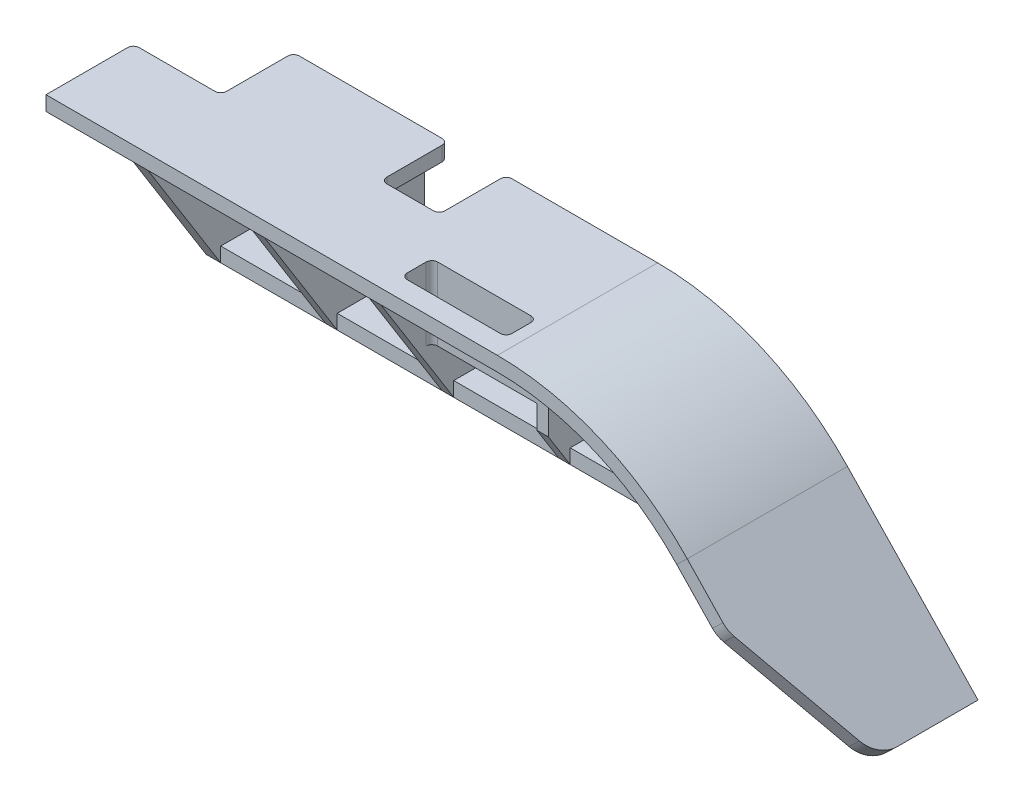
SolidWorks part; units mm, degrees
ref_plane "Front" through (0, 0, 0) normal (0, 0, 1) x (1, 0, 0)
ref_plane "Top" through (0, 0, 0) normal (0, 1, 0) x (1, 0, 0)
ref_plane "Right" through (0, 0, 0) normal (1, 0, 0) x (0, 0, -1)
sketch "Sketch1" plane through (0, 0, 0) normal (0, 1, 0) x (1, 0, 0)
  line L1 (-77.5, 27.5) -> (77.5, 27.5)
  line L2 (-77.5, 27.5) -> (-77.5, -27.5)
  line L3 (-77.5, -27.5) -> (77.5, -27.5)
  line L4 (77.5, 27.5) -> (77.5, -27.5)
  line L5 (-77.5, 27.5) -> (77.5, -27.5) construction
  line L6 (-77.5, -27.5) -> (77.5, 27.5) construction
  point P0 (0, 0)
  dimension "D1" = 155
  dimension "D2" = 55
extrude "Boss-Extrude1" add sketch "Sketch1" along normal blind 5
ref_plane "Plane1" through (0, -40, 0) normal (0, 1, 0) x (1, 0, 0)
sketch "Sketch2" plane through (0, 5, 0) normal (0, 1, 0) x (1, 0, 0)
  line L1 (-77.5, 27.5) -> (-47.5, 27.5)
  line L2 (-77.5, 27.5) -> (-77.5, 2.5)
  line L3 (-77.5, 2.5) -> (-47.5, 2.5)
  line L4 (-47.5, 27.5) -> (-47.5, 2.5)
  dimension "D1" = 25
  dimension "D2" = 30
extrude "Cut-Extrude2" cut sketch "Sketch2" against normal up to surface (5 mm away) up to face at (0, 0, 0)
sketch "Sketch3" plane through (0, 0, 0) normal (0, -1, 0) x (1, 0, 0)
  line L6 (-77.5, 27.5) -> (77.5, 27.5) construction
  line L7 (-47.5, -27.5) -> (-42.5, -27.5)
  line L8 (-47.5, -27.5) -> (-47.5, 27.5)
  line L9 (-47.5, 27.5) -> (-42.5, 27.5)
  line L10 (-42.5, -27.5) -> (-42.5, 27.5)
  dimension "D1" = 5
extrude "Boss-Extrude2" add sketch "Sketch3" along normal up to surface (40 mm away) contours L10 L9 L8 L7 up to plane "Plane1"
sketch "Sketch9" plane through (0, 0, 27.5) normal (0, 0, 1) x (1, 0, 0)
  line L0 (77.5, 5) -> (187.5, 5) construction
  line L1 (187.5, 5) -> (187.5, -70) construction
  line L2 (-77.5, 5) -> (77.5, 5) construction
  line L3 (187.5, -70) -> (142.6724, -22.931)
  line L4 (77.5, 5) -> (77.5, 0) construction
  arc A1 (142.6724, -22.931) -> (77.5, 5) centre (77.5, -85) ccw
  point P4 (91.2465, 5)
  point P5 (0, 0)
  point P6 (0, 0)
  point P12 (141.796, 5)
  point P13 (0, 0)
  dimension "D1" = 110
  dimension "D2" = 75
sketch "Sketch10" plane through (77.5, 0, 0) normal (1, 0, 0) x (0, 0, -1)
  line L1 (27.5, 5) -> (-27.5, 5)
  line L2 (27.5, 5) -> (27.5, 0)
  line L3 (27.5, 0) -> (-27.5, 0)
  line L4 (-27.5, 5) -> (-27.5, 0)
sweep "Sweep1" add profiles "Sketch10" path "Sketch9"
sketch "Sketch14" plane through (0, -40, 0) normal (0, 1, 0) x (1, 0, 0)
  line L1 (-42.5, 27.5) -> (82.5, 27.5)
  line L2 (-42.5, 27.5) -> (-42.5, -2.5)
  line L3 (-42.5, -2.5) -> (82.5, -2.5)
  line L4 (82.5, 27.5) -> (82.5, -2.5)
  dimension "D1" = 125
  dimension "D2" = 30
extrude "Boss-Extrude7" add sketch "Sketch14" along normal blind 5
sketch "Sketch16" plane through (82.5, 0, 0) normal (1, 0, 0) x (0, 0, -1)
  line L1 (27.5, -35) -> (-2.5, -35)
  line L2 (27.5, -35) -> (27.5, -40)
  line L3 (27.5, -40) -> (-2.5, -40)
  line L4 (-2.5, -35) -> (-2.5, -40)
extrude "Boss-Extrude8" add sketch "Sketch16" along normal up to surface (64.7619 mm away) up to face at (161.4655, -49.9138, 0)
sketch "Sketch19" plane through (0, 0, 0) normal (0, -1, 0) x (1, 0, 0)
  line L9 (-42.5, 27.5) -> (77.5, 27.5) construction
  line L15 (77.5, -27.5) -> (73.5, -27.5)
  line L16 (77.5, -27.5) -> (77.5, 27.5)
  line L17 (77.5, 27.5) -> (73.5, 27.5)
  line L18 (73.5, -27.5) -> (73.5, 27.5)
  line L19 (37.5, -27.5) -> (37.5, 27.5)
  line L20 (37.5, -27.5) -> (33.5, -27.5)
  line L21 (33.5, -27.5) -> (33.5, 27.5)
  line L22 (37.5, 27.5) -> (33.5, 27.5)
  line L23 (-2.5, -27.5) -> (-2.5, 27.5)
  line L24 (-2.5, -27.5) -> (-6.5, -27.5)
  line L25 (-6.5, -27.5) -> (-6.5, 27.5)
  line L26 (-2.5, 27.5) -> (-6.5, 27.5)
  line L27 (77.5, -27.5) -> (37.5, -27.5) construction
  dimension "D1" = 4
  dimension "D2" = 40
extrude "Boss-Extrude9" add sketch "Sketch19" along normal up to surface (40 mm away) up to face at (20.6746, -40, 0.8333)
sketch "Sketch17" plane through (-47.5, 0, 0) normal (-1, 0, 0) x (0, 0, 1)
  line L0 (27.5, 0) -> (2.5, -40)
  line L1 (2.5, -40) -> (27.5, -40)
  line L2 (27.5, -40) -> (27.5, 0) construction
  line L3 (27.5, -40) -> (27.5, 0)
  line L5 (27.5, -40) -> (-27.5, -40) construction
  dimension "D1" = 0
extrude "Cut-Extrude4" cut sketch "Sketch17" against normal up to surface (125 mm away) up to face at (77.5, -25, 0.8333)
sketch "Sketch18" plane through (0, -35, 0) normal (0, 1, 0) x (1, 0, 0)
  line L0 (-47.5, -2.5) -> (-47.5, 27.5) construction
  line L1 (152.0238, 27.5) -> (-47.5, 27.5) construction
  circle A0 centre (-30.5, 17) radius 1.75
  circle A1 centre (69.5, 17) radius 1.75
  point P4 (0, 0)
  dimension "D1" = 3.5
  dimension "D2" = 17
  dimension "D3" = 100
  dimension "D4" = 10.5
extrude "Cut-Extrude5" cut sketch "Sketch18" against normal up to surface (5 mm away) up to face at (34.5043, -40, -2.9545)
sketch "Sketch20" plane through (0, -35, 0) normal (0, 1, 0) x (1, 0, 0)
  line L0 (77.5, 27.5) -> (77.5, -2.5) construction
  line L1 (81.5, 1.5) -> (119.5, 1.5)
  line L2 (81.5, 1.5) -> (81.5, 17.5)
  line L3 (81.5, 17.5) -> (119.5, 17.5)
  line L4 (119.5, 1.5) -> (119.5, 17.5)
  line L5 (77.5, -2.5) -> (147.2619, -2.5) construction
  point P5 (0, 0)
  dimension "D1" = 16
  dimension "D2" = 4
  dimension "D3" = 4
  dimension "D4" = 38
extrude "Cut-Extrude6" cut sketch "Sketch20" against normal up to surface (5 mm away) up to face at (-30.5, -40, -15.25)
fillet "Fillet1" radius 5 4 edges at (119.5, -37.5, -17.5) (119.5, -37.5, -1.5) (81.5, -37.5, -1.5) (81.5, -37.5, -17.5)
sketch "Sketch21" plane through (73.5, 0, 0) normal (-1, 0, 0) x (0, 0, 1)
  line L6 (27.5, 0) -> (-27.5, 0) construction
  line L11 (10, 0) -> (5, 0)
  line L12 (10, 0) -> (10, -20)
  line L13 (10, -20) -> (5, -20)
  line L14 (5, 0) -> (5, -20)
  dimension "D1" = 5
  dimension "D2" = 17.5
  dimension "D3" = 20
extrude "Boss-Extrude10" add sketch "Sketch21" along normal up to surface (36 mm away) up to face at (37.5, -22, -4.5)
sketch "Sketch22" plane through (73.5, 0, 0) normal (-1, 0, 0) x (0, 0, 1)
  line L2 (10, -28) -> (27.5, 0)
  line L3 (27.5, 0) -> (10, 0)
  line L4 (10, 0) -> (10, -28)
  line L5 (2.5, -40) -> (27.5, 0) construction
  point P3 (0, 0)
  point P4 (0, 0)
  point P5 (0, 0)
  point P9 (0, 0)
  point P10 (10.5429, -28.0917)
  point P11 (0, 0)
  point P14 (0, 0)
extrude "Cut-Extrude7" cut sketch "Sketch22" against normal up to surface (4 mm away) up to face at (77.5, -22, -4.5)
sketch "Sketch23" plane through (0, 0, 0) normal (0, -1, 0) x (1, 0, 0)
  line L7 (37.5, 10) -> (73.5, 10)
  line L8 (37.5, 10) -> (37.5, 20.5)
  line L9 (37.5, 20.5) -> (73.5, 20.5)
  line L10 (73.5, 10) -> (73.5, 20.5)
  line L14 (37.5, 10) -> (73.5, 10) construction
  line L15 (77.5, 27.5) -> (77.5, 10) construction
  line L16 (37.5, 10) -> (37.5, 27.5) construction
  dimension "D1" = 10.5
  dimension "D2" = 4
extrude "Cut-Extrude8" cut sketch "Sketch23" against normal up to surface (5 mm away) up to face at (-15.8333, 5, -0.8333)
fillet "Fillet2" radius 2 4 edges at (73.5, 2.5, 20.5) (73.5, 2.5, 10) (37.5, 2.5, 20.5) (37.5, -7.5, 10)
sketch "Sketch24" plane through (0, 0, 0) normal (0, -1, 0) x (1, 0, 0)
  line L0 (33.5, -27.5) -> (-2.5, -27.5) construction
  line L1 (25.5, -27.5) -> (5.5, -27.5)
  line L2 (25.5, -27.5) -> (25.5, -4.5)
  line L3 (25.5, -4.5) -> (5.5, -4.5)
  line L4 (5.5, -27.5) -> (5.5, -4.5)
  line L5 (-47.5, -2.5) -> (-47.5, -27.5) construction
  dimension "D1" = 20
  dimension "D2" = 53
  dimension "D3" = 23
extrude "Cut-Extrude9" cut sketch "Sketch24" against normal up to surface (5 mm away) up to face at (55.5, 5, 15.25)
fillet "Fillet3" radius 2 7 edges at (-47.5, 2.5, -2.5) (5.5, 2.5, -4.5) (5.5, 2.5, -27.5) (25.5, 2.5, -4.5) (25.5, 2.5, -27.5) (-47.5, -17.5, -27.5) (-77.5, 2.5, -2.5)
chamfer "Chamfer1" distance 45 angle 25 1 edges at (185.6897, -71.7241, 27.5) first distance on face at (163.2759, -48.1897, 27.5)
fillet "Fillet4" radius 10 2 edges at (154.6552, -39.1379, 27.5) (185.6897, -71.7241, 6.5162)
